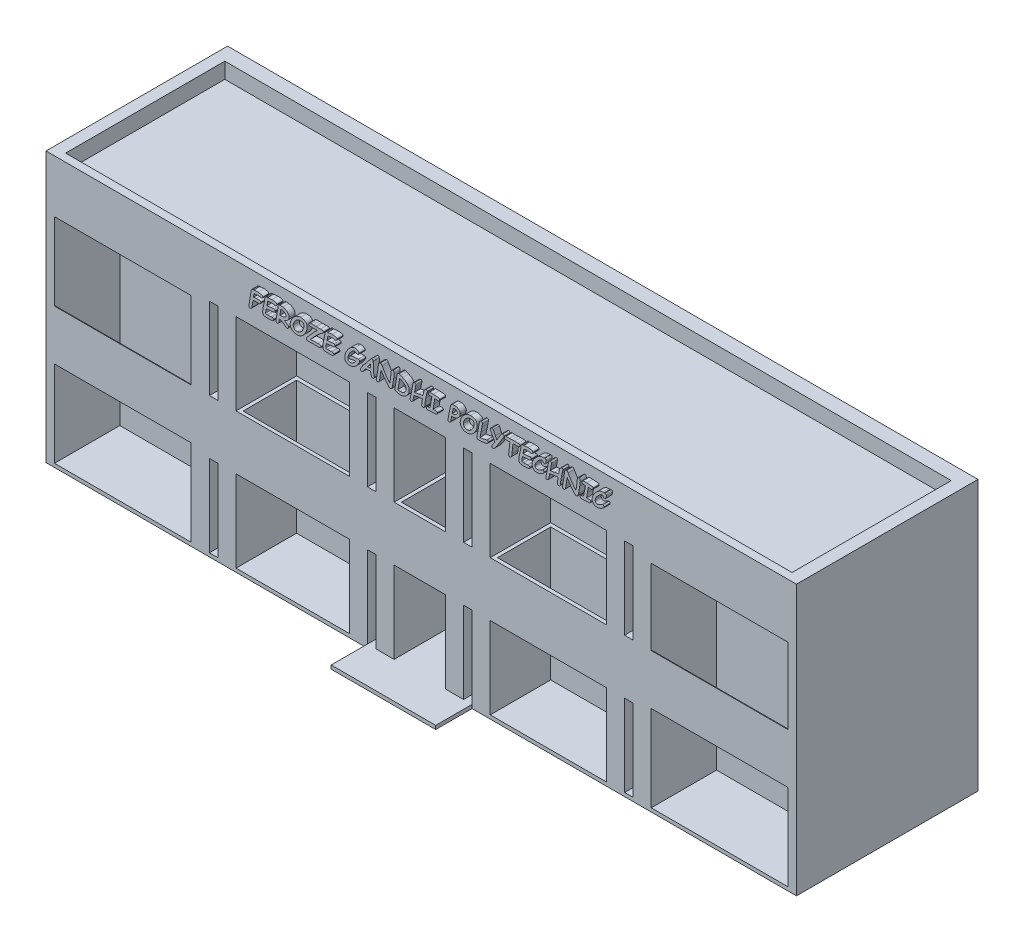
SolidWorks part; units mm, degrees
ref_plane "Front Plane" through (0, 0, 0) normal (0, 0, 1) x (1, 0, 0)
ref_plane "Top Plane" through (0, 0, 0) normal (0, 1, 0) x (1, 0, 0)
ref_plane "Right Plane" through (0, 0, 0) normal (1, 0, 0) x (0, 0, -1)
sketch "Sketch1" plane through (0, 0, 0) normal (0, 0, 1) x (1, 0, 0)
  line L1 (-190, -90) -> (190, -90)
  line L2 (-190, -90) -> (-190, 90)
  line L3 (-190, 90) -> (190, 90)
  line L4 (190, -90) -> (190, 90)
  line L5 (-190, -90) -> (190, 90) construction
  line L6 (-190, 90) -> (190, -90) construction
  point P0 (0, 0)
  dimension "D1" = 180
  dimension "D2" = 380
extrude "Boss-Extrude1" add sketch "Sketch1" along normal blind 100
sketch "Sketch2" plane through (0, 0, 100) normal (0, 0, 1) x (1, 0, 0)
  line L0 (0, -90) -> (0, 90) construction
  line L1 (-190, -90) -> (190, -90) construction
  line L2 (190, 90) -> (-190, 90) construction
  line L3 (0, 0) -> (20, 0) construction
  line L4 (0, 0) -> (-22.3942, 0) construction
  line L5 (-22.3942, 90) -> (-22.3942, -90) construction
  line L6 (-22.3942, -90) -> (20, -90) construction
  line L7 (20, -90) -> (20, 90) construction
  line L9 (-190, -90) -> (-175, -90)
  line L10 (-190, -90) -> (-190, 90)
  line L11 (-190, 90) -> (-175, 90)
  line L12 (-175, -90) -> (-175, 90)
  line L13 (-168, -90) -> (-153, -90)
  line L14 (-168, -90) -> (-168, 90)
  line L15 (-168, 90) -> (-153, 90)
  line L16 (-153, -90) -> (-153, 90)
  line L17 (-22.3942, -90) -> (-37.3942, -90)
  line L18 (-22.3942, -90) -> (-22.3942, 90)
  line L19 (-22.3942, 90) -> (-37.3942, 90)
  line L20 (-37.3942, -90) -> (-37.3942, 90)
  line L21 (-44.3942, -90) -> (-59.3942, -90)
  line L22 (-44.3942, -90) -> (-44.3942, 90)
  line L23 (-44.3942, 90) -> (-59.3942, 90)
  line L24 (-59.3942, -90) -> (-59.3942, 90)
  line L25 (20, -90) -> (35, -90)
  line L26 (20, -90) -> (20, 90)
  line L27 (20, 90) -> (35, 90)
  line L28 (35, -90) -> (35, 90)
  line L29 (42, -90) -> (57, -90)
  line L30 (42, -90) -> (42, 90)
  line L31 (42, 90) -> (57, 90)
  line L32 (57, -90) -> (57, 90)
  line L37 (190, -90) -> (175, -90)
  line L38 (190, -90) -> (190, 90)
  line L39 (190, 90) -> (175, 90)
  line L40 (175, -90) -> (175, 90)
  line L41 (168, -90) -> (153, -90)
  line L42 (168, -90) -> (168, 90)
  line L43 (168, 90) -> (153, 90)
  line L44 (153, -90) -> (153, 90)
  dimension "D1" = 15
  dimension "D2" = 15
  dimension "D3" = 15
  dimension "D4" = 15
  dimension "D5" = 7
  dimension "D6" = 7
  dimension "D7" = 15
  dimension "D8" = 15
  dimension "D9" = 7
  dimension "D10" = 15
  dimension "D11" = 15
  dimension "D12" = 7
extrude "Boss-Extrude2" add sketch "Sketch2" along normal blind 50 contours L10 L9 L12 L11 | L14 L13 L16 L15 | L22 L21 L24 L23 | L18 L17 L20 L19 | L26 L25 L28 L27 | L30 L29 L32 L31 | L42 L41 L44 L43 | L38 L37 L40 L39
sketch "Sketch3" plane through (0, 0, 150) normal (0, 0, 1) x (1, 0, 0)
  line L0 (-190, -90) -> (-190, 90) construction
  line L1 (-190, 0) -> (201.0298, 0) construction
  line L2 (-190, 45) -> (201.0298, 45) construction
  line L3 (-190, -45) -> (201.0298, -45) construction
  line L4 (190, -90) -> (190, 90) construction
  line L5 (-190, -22.5) -> (190, -22.5)
  line L6 (-190, -22.5) -> (-190, 22.5)
  line L7 (-190, 22.5) -> (190, 22.5)
  line L8 (190, -22.5) -> (190, 22.5)
  line L9 (-190, -22.5) -> (190, 22.5) construction
  line L10 (-190, 22.5) -> (190, -22.5) construction
  point P9 (0, 0)
  dimension "D1" = 45
  dimension "D2" = 45
  dimension "D3" = 90
  dimension "D4" = 45
  dimension "D5" = 22.5
extrude "Boss-Extrude3" add sketch "Sketch3" against normal blind 50
sketch "Sketch4" plane through (0, 0, 150) normal (0, 0, 1) x (1, 0, 0)
  line L1 (-190, 90) -> (189.5, 90)
  line L2 (-190, 90) -> (-190, 135)
  line L3 (-190, 135) -> (189.5, 135)
  line L4 (189.5, 90) -> (189.5, 135)
  dimension "D1" = 45
sketch "Sketch5" plane through (0, -90, 0) normal (0, -1, 0) x (1, 0, 0)
  line L0 (-190, 150) -> (-190, 0) construction
  line L1 (-185, 7.4092) -> (181.0583, 7.4092)
  line L2 (-185, 7.4092) -> (-185, 94.4231)
  line L3 (-185, 94.4231) -> (181.0583, 94.4231)
  line L4 (181.0583, 7.4092) -> (181.0583, 94.4231)
  dimension "D1" = 5
extrude "Cut-Extrude1" cut sketch "Sketch5" against normal blind 220
sketch "Sketch6" plane through (0, -22.5, 0) normal (0, -1, 0) x (1, 0, 0)
  line L0 (-153, 150) -> (-153, 100) construction
  line L1 (-150, 103) -> (-62.3942, 103)
  line L2 (-150, 103) -> (-150, 147.176)
  line L3 (-150, 147.176) -> (-62.3942, 147.176)
  line L4 (-62.3942, 103) -> (-62.3942, 147.176)
  line L5 (60, 103) -> (150, 103)
  line L6 (60, 103) -> (60, 147)
  line L7 (60, 147) -> (150, 147)
  line L8 (150, 103) -> (150, 147)
  line L9 (-19.3942, 103) -> (17, 103)
  line L10 (-19.3942, 103) -> (-19.3942, 147)
  line L11 (-19.3942, 147) -> (17, 147)
  line L12 (17, 103) -> (17, 147)
  line L13 (-59.3942, 100) -> (-59.3942, 150) construction
  line L14 (-153, 100) -> (-59.3942, 100) construction
  line L15 (-22.3942, 150) -> (-22.3942, 100) construction
  line L16 (20, 100) -> (20, 150) construction
  line L17 (-22.3942, 100) -> (20, 100) construction
  line L18 (-22.3942, 150) -> (20, 150) construction
  line L19 (57, 100) -> (57, 150) construction
  line L20 (153, 100) -> (153, 150) construction
  line L21 (57, 100) -> (153, 100) construction
  line L22 (57, 150) -> (153, 150) construction
  point P14 (-62.3942, 125.088)
  dimension "D1" = 3
  dimension "D2" = 3
  dimension "D3" = 3
  dimension "D4" = 3
  dimension "D5" = 3
  dimension "D6" = 3
  dimension "D7" = 3
  dimension "D8" = 3
  dimension "D9" = 3
  dimension "D10" = 3
  dimension "D11" = 3
extrude "Cut-Extrude2" cut sketch "Sketch6" against normal blind 50
sketch "Sketch8" plane through (0, -90, 0) normal (0, -1, 0) x (1, 0, 0)
  line L1 (-190, 0) -> (190, 0)
  line L2 (-190, 0) -> (-190, 150)
  line L3 (-190, 150) -> (190, 150)
  line L4 (190, 0) -> (190, 150)
extrude "Boss-Extrude5" add sketch "Sketch8" along normal blind 3
sketch "Sketch13" plane through (0, 0, 150) normal (0, 0, 1) x (1, 0, 0)
  text T0 "FEROZE GANDHI POLYTECHNIC" font "Comic Sans MS" height in points 48
extrude "Boss-Extrude10" add sketch "Sketch13" along normal blind 5
sketch "Sketch14" plane through (0, 0, 150) normal (0, 0, 1) x (1, 0, 0)
  line L0 (-37.3942, -90) -> (-37.3942, -22.5) construction
  line L1 (-22.3942, -90) -> (-22.3942, -22.5) construction
  line L2 (35, -90) -> (35, -22.5) construction
  line L3 (20, -90) -> (20, -22.5) construction
  circle A0 centre (-29.3942, -56.25) radius 3
  circle A1 centre (27, -56.25) radius 3
  point P12 (20, -56.25)
  dimension "D1" = 6
  dimension "D2" = 6
  dimension "D3" = 8
  dimension "D4" = 7
  dimension "D5" = 8
  dimension "D6" = 7
sketch "Sketch16" plane through (0, 0, 150) normal (0, 0, 1) x (1, 0, 0)
  line L5 (190, -93) -> (-190, -93) construction
  line L6 (-44.3942, -90) -> (41.9944, -90)
  line L7 (-44.3942, -90) -> (-44.3942, -93)
  line L8 (-44.3942, -93) -> (41.9944, -93)
  line L9 (41.9944, -90) -> (41.9944, -93)
extrude "Boss-Extrude14" add sketch "Sketch16" along normal blind 30
sketch "Sketch71" plane through (0, 90, 0) normal (0, 1, 0) x (1, 0, 0)
  line L0 (-154.6921, -147.4581) -> (-154.6921, -95.6557)
  line L5 (-166.3812, -95.6557) -> (-154.6921, -95.6557)
  line L6 (-166.3812, -95.6557) -> (-166.3812, -147.4581)
  line L7 (-166.3812, -147.4581) -> (-154.6921, -147.4581)
  line L15 (-177.1895, -95.6557) -> (-187.9442, -95.6557)
  line L16 (-177.1895, -95.6557) -> (-177.1895, -147.4581)
  line L17 (-177.1895, -147.4581) -> (-187.9442, -147.4581)
  line L18 (-187.9442, -95.6557) -> (-187.9442, -147.4581)
  line L19 (-57.5291, -95.6557) -> (-46.8167, -95.6557)
  line L20 (-57.5291, -95.6557) -> (-57.5291, -147.4581)
  line L21 (-57.5291, -147.4581) -> (-46.8167, -147.4581)
  line L22 (-46.8167, -95.6557) -> (-46.8167, -147.4581)
  line L23 (-34.9882, -95.6557) -> (-24.2534, -95.6557)
  line L24 (-34.9882, -95.6557) -> (-34.9882, -147.4581)
  line L25 (-34.9882, -147.4581) -> (-24.2534, -147.4581)
  line L26 (-24.2534, -95.6557) -> (-24.2534, -147.4581)
  line L27 (21.6105, -95.6557) -> (32.7032, -95.6557)
  line L28 (21.6105, -95.6557) -> (21.6105, -147.4581)
  line L29 (21.6105, -147.4581) -> (32.7032, -147.4581)
  line L30 (32.7032, -95.6557) -> (32.7032, -147.4581)
  line L31 (44.1513, -95.6557) -> (55.3117, -95.6557)
  line L32 (44.1513, -95.6557) -> (44.1513, -147.4581)
  line L33 (44.1513, -147.4581) -> (55.3117, -147.4581)
  line L34 (55.3117, -95.6557) -> (55.3117, -147.4581)
  line L35 (154.3749, -95.6557) -> (165.4226, -95.6557)
  line L36 (154.3749, -95.6557) -> (154.3749, -147.4581)
  line L37 (154.3749, -147.4581) -> (165.4226, -147.4581)
  line L38 (165.4226, -95.6557) -> (165.4226, -147.4581)
  line L39 (177.2737, -95.6557) -> (187.4052, -95.6557)
  line L40 (177.2737, -95.6557) -> (177.2737, -147.4581)
  line L41 (177.2737, -147.4581) -> (187.4052, -147.4581)
  line L42 (187.4052, -95.6557) -> (187.4052, -147.4581)
extrude "Cut-Extrude9" cut sketch "Sketch71" against normal blind 180
sketch "Sketch72" plane through (0, 90, 0) normal (0, 1, 0) x (1, 0, 0)
  line L0 (-185, -7.4092) -> (181.0583, -7.4092) construction
  line L1 (188.1794, -1.15) -> (182.7769, -1.15)
  line L2 (188.1794, -1.15) -> (188.1794, -93.9506)
  line L3 (188.1794, -93.9506) -> (182.7769, -93.9506)
  line L4 (182.7769, -1.15) -> (182.7769, -93.9506)
  line L9 (190, 0) -> (-190, 0) construction
  line L11 (-190, -150) -> (-190, 0) construction
  line L12 (178.717, -1.5) -> (-188.7, -1.5)
  line L13 (-186.0556, -7.6936) -> (-188.7, -7.6936)
  line L14 (-186.0556, -7.6936) -> (-186.0556, -93.9506)
  line L15 (-186.0556, -93.9506) -> (-188.7, -93.9506)
  line L16 (-188.7, -7.6936) -> (-188.7, -93.9506)
  line L17 (178.717, -1.5) -> (178.717, -5.9092)
  line L18 (178.717, -5.9092) -> (-188.7, -5.9092)
  line L19 (-188.7, -1.5) -> (-188.7, -5.9092)
  dimension "D1" = 1.5
  dimension "D2" = 1.5
  dimension "D3" = 1.3
  dimension "D4" = 1.3
  dimension "D5" = 4.0598
extrude "Cut-Extrude10" cut sketch "Sketch72" against normal blind 180
sketch "Sketch73" plane through (0, 90, 0) normal (0, 1, 0) x (1, 0, 0)
  line L0 (-34.9882, -95.6557) -> (-34.9882, -147.4581) construction
  line L5 (-153.6921, -95.4231) -> (-58.5291, -95.4231)
  line L6 (-153.6921, -95.4231) -> (-153.6921, -99)
  line L7 (-153.6921, -99) -> (-58.5291, -99)
  line L8 (-58.5291, -95.4231) -> (-58.5291, -99)
  line L13 (-24.2534, -147.4581) -> (-24.2534, -95.6557) construction
  line L14 (56.3117, -99) -> (153.3749, -99)
  line L15 (56.3117, -99) -> (56.3117, -95.4231)
  line L16 (56.3117, -95.4231) -> (153.3749, -95.4231)
  line L17 (153.3749, -99) -> (153.3749, -95.4231)
  line L18 (166.4226, -95.4231) -> (176.2737, -95.4231)
  line L19 (166.4226, -95.4231) -> (166.4226, -99)
  line L20 (166.4226, -99) -> (176.2737, -99)
  line L21 (176.2737, -95.4231) -> (176.2737, -99)
  line L22 (34.2032, -95.9231) -> (42.6513, -95.9231)
  line L23 (34.2032, -95.9231) -> (34.2032, -98.5)
  line L24 (34.2032, -98.5) -> (42.6513, -98.5)
  line L25 (42.6513, -95.9231) -> (42.6513, -98.5)
  line L26 (-22.7534, -95.9231) -> (20.1105, -95.9231)
  line L27 (-22.7534, -95.9231) -> (-22.7534, -98.5)
  line L28 (-22.7534, -98.5) -> (20.1105, -98.5)
  line L29 (20.1105, -95.9231) -> (20.1105, -98.5)
  line L30 (21.6105, -95.6557) -> (21.6105, -147.4581) construction
  line L31 (181.0583, -94.4231) -> (-185, -94.4231) construction
  line L32 (20, -100) -> (-22.3942, -100) construction
  line L33 (32.7032, -147.4581) -> (32.7032, -95.6557) construction
  line L34 (44.1513, -95.6557) -> (44.1513, -147.4581) construction
  line L35 (42, -100) -> (35, -100) construction
  line L36 (-37.3942, -100) -> (-44.3942, -100) construction
  line L37 (-59.3942, -100) -> (-153, -100) construction
  line L38 (-154.6921, -147.4581) -> (-154.6921, -95.6557) construction
  line L39 (-46.8167, -147.4581) -> (-46.8167, -95.6557) construction
  line L40 (-45.3167, -98.5) -> (-36.4882, -98.5)
  line L41 (-45.3167, -98.5) -> (-45.3167, -95.9231)
  line L42 (-45.3167, -95.9231) -> (-36.4882, -95.9231)
  line L43 (-36.4882, -98.5) -> (-36.4882, -95.9231)
  line L44 (-57.5291, -95.6557) -> (-57.5291, -147.4581) construction
  line L48 (-166.3812, -95.6557) -> (-166.3812, -147.4581) construction
  line L49 (-176.1895, -95.4231) -> (-167.3812, -95.4231)
  line L50 (-176.1895, -95.4231) -> (-176.1895, -99)
  line L51 (-176.1895, -99) -> (-167.3812, -99)
  line L52 (-167.3812, -95.4231) -> (-167.3812, -99)
  line L53 (165.4226, -147.4581) -> (165.4226, -95.6557) construction
  line L54 (177.2737, -95.6557) -> (177.2737, -147.4581) construction
  line L55 (175, -100) -> (168, -100) construction
  line L56 (154.3749, -95.6557) -> (154.3749, -147.4581) construction
  line L57 (153, -100) -> (57, -100) construction
  line L58 (55.3117, -147.4581) -> (55.3117, -95.6557) construction
  dimension "D1" = 1.5
  dimension "D2" = 1.5
  dimension "D3" = 1.5
  dimension "D4" = 1.5
  dimension "D5" = 1.5
  dimension "D6" = 1.5
  dimension "D7" = 1.5
  dimension "D8" = 1.5
  dimension "D9" = 1.5
  dimension "D10" = 1.5
  dimension "D11" = 1.5
  dimension "D12" = 1.5
  dimension "D13" = 1
  dimension "D14" = 1
  dimension "D15" = 1
  dimension "D16" = 1
  dimension "D17" = 1
  dimension "D18" = 1
  dimension "D19" = 1
  dimension "D20" = 1
  dimension "D21" = 1
  dimension "D22" = 1
  dimension "D23" = 1
  dimension "D24" = 1
  dimension "D25" = 1
extrude "Cut-Extrude11" cut sketch "Sketch73" against normal blind 180
sketch "Sketch74" plane through (190, 0, 0) normal (1, 0, 0) x (0, 0, -1)
  line L1 (-150, -93) -> (0, -93)
  line L2 (-150, -93) -> (-150, 90)
  line L3 (-150, 90) -> (0, 90)
  line L4 (0, -93) -> (0, 90)
extrude "Boss-Extrude39" add sketch "Sketch74" along normal blind 120
sketch "Sketch75" plane through (-190, 0, 0) normal (-1, 0, 0) x (0, 0, 1)
  line L1 (150, -93) -> (0, -93)
  line L2 (150, -93) -> (150, 90)
  line L3 (150, 90) -> (0, 90)
  line L4 (0, -93) -> (0, 90)
extrude "Boss-Extrude40" add sketch "Sketch75" along normal blind 120
sketch "Sketch76" plane through (0, 0, 150) normal (0, 0, 1) x (1, 0, 0)
  line L10 (-175, 22.5) -> (-175, 90) construction
  line L11 (-190, -90) -> (-303, -90)
  line L12 (-190, -90) -> (-190, 86.5)
  line L13 (-190, 86.5) -> (-303, 86.5)
  line L14 (-303, -90) -> (-303, 86.5)
  line L22 (-310, -93) -> (-310, 90) construction
  line L23 (-310, 90) -> (-175, 90) construction
  line L25 (175, -90) -> (175, -22.5) construction
  line L26 (303, -90) -> (190, -90)
  line L27 (303, -90) -> (303, 85)
  line L28 (303, 85) -> (190, 85)
  line L29 (190, -90) -> (190, 85)
  line L31 (310, 90) -> (310, -93) construction
  line L32 (310, 90) -> (175, 90) construction
  line L33 (310, -93) -> (41.9944, -93) construction
  dimension "D1" = 15
  dimension "D2" = 15
  dimension "D3" = 3
  dimension "D4" = 7
  dimension "D5" = 3.5
  dimension "D6" = 7
  dimension "D8" = 5
extrude "Cut-Extrude13" cut sketch "Sketch76" against normal blind 54
sketch "Sketch77" plane through (0, 0, 150) normal (0, 0, 1) x (1, 0, 0)
  line L5 (-175, 22.5) -> (-315.4311, 22.5) construction
  line L6 (-310, -93) -> (-310, 90) construction
  line L7 (-310, 22.5) -> (310, 22.5)
  line L8 (-310, 22.5) -> (-310, -18.8926)
  line L9 (-310, -18.8926) -> (310, -18.8926)
  line L10 (310, 22.5) -> (310, -18.8926)
  line L11 (310, 90) -> (310, -93) construction
extrude "Boss-Extrude41" add sketch "Sketch77" against normal blind 0.5
sketch "Sketch78" [suppressed] plane through (0, 90, 0) normal (0, 1, 0) x (1, 0, 0)
  line L0 (310, 0) -> (310, -150) construction
  line L1 (-310, 0) -> (310, 0)
  line L2 (-310, 0) -> (-310, -150)
  line L3 (-310, -150) -> (310, -150)
  line L4 (310, 0) -> (310, -150)
  line L5 (310, -150) -> (175, -150) construction
extrude "Boss-Extrude42" [suppressed] add sketch "Sketch78" along normal blind 50
sketch "Sketch79" [suppressed] plane through (0, 140, 0) normal (0, 1, 0) x (1, 0, 0)
  line L1 (-303.4477, -7.7846) -> (304.9464, -7.7846)
  line L2 (-303.4477, -7.7846) -> (-303.4477, -143.44)
  line L3 (-303.4477, -143.44) -> (304.9464, -143.44)
  line L4 (304.9464, -7.7846) -> (304.9464, -143.44)
extrude "Cut-Extrude14" [suppressed] cut sketch "Sketch79" against normal blind 47
sketch "Sketch80" plane through (0, 90, 0) normal (0, 1, 0) x (1, 0, 0)
  line L1 (-310, 0) -> (310, 0)
  line L2 (-310, 0) -> (-310, -150)
  line L3 (-310, -150) -> (310, -150)
  line L4 (310, 0) -> (310, -150)
extrude "Boss-Extrude43" add sketch "Sketch80" along normal blind 40
sketch "Sketch81" plane through (0, 130, 0) normal (0, 1, 0) x (1, 0, 0)
  line L1 (-300.3647, -11.8953) -> (299.808, -11.8953)
  line L2 (-300.3647, -11.8953) -> (-300.3647, -143.44)
  line L3 (-300.3647, -143.44) -> (299.808, -143.44)
  line L4 (299.808, -11.8953) -> (299.808, -143.44)
extrude "Cut-Extrude15" cut sketch "Sketch81" against normal blind 38
sketch "Sketch82" plane through (0, 92, 0) normal (0, 1, 0) x (1, 0, 0)
  line L0 (-300.3647, -143.44) -> (299.808, -143.44) construction
  line L1 (-300.3647, -11.8953) -> (299.808, -11.8953)
  line L2 (-300.3647, -11.8953) -> (-300.3647, -143.44)
  line L3 (-300.3647, -143.44) -> (299.808, -143.44)
  line L4 (299.808, -11.8953) -> (299.808, -143.44)
extrude "Boss-Extrude44" add sketch "Sketch82" along normal blind 25
